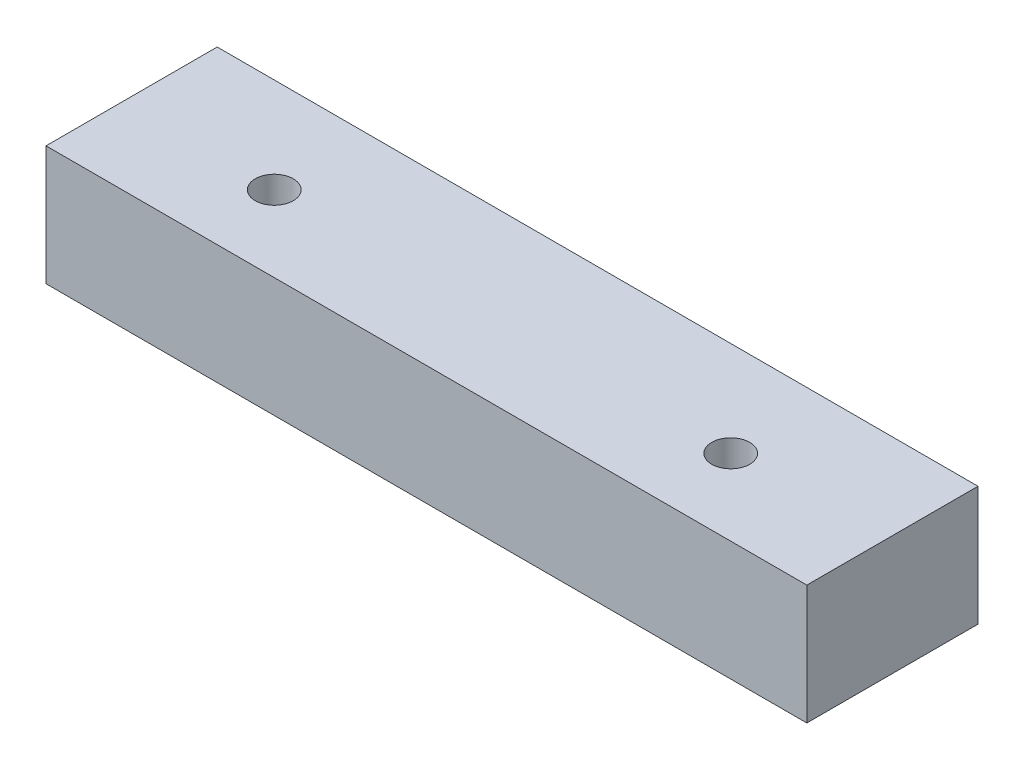
SolidWorks part; units mm, degrees
ref_plane "Front Plane" through (0, 0, 0) normal (0, 0, 1) x (1, 0, 0)
ref_plane "Top Plane" through (0, 0, 0) normal (0, 1, 0) x (1, 0, 0)
ref_plane "Right Plane" through (0, 0, 0) normal (1, 0, 0) x (0, 0, -1)
sketch "Sketch1" plane through (0, 0, 0) normal (0, 1, 0) x (1, 0, 0)
  line L0 (0, 0) -> (0, 9)
  line L1 (0, 9) -> (40, 9)
  line L2 (40, 9) -> (40, 0)
  line L3 (0, 0) -> (40, 0)
  dimension "D1" = 40
  dimension "D2" = 9
extrude "Boss-Extrude1" add sketch "Sketch1" along normal blind 6.28
sketch "Sketch2" plane through (0, 6.28, 0) normal (0, 1, 0) x (1, 0, 0)
  line L0 (0, 9) -> (8, 9)
  line L1 (40, 9) -> (0, 9) construction
  line L2 (8, 9) -> (8, 4)
  line L3 (8, 4) -> (32, 4)
  line L4 (0, 0) -> (0, 2.2) construction
  line L5 (0, 9) -> (0, 0) construction
  line L6 (0, 2.2) -> (19.4811, 2.2) construction
  line L7 (0, 2.2) -> (5, 2.2)
  line L8 (5, 2.2) -> (8, 2.2)
  line L9 (0, 0) -> (0, 0.75)
  line L10 (5, 2.2) -> (0, 0.75)
  line L11 (0, 0.75) -> (0, 2.2)
  line L12 (0, 0.75) -> (3, 0.75)
  line L13 (3, 0.75) -> (8, 2.2)
  line L14 (0, 0.75) -> (12.9505, 0.75) construction
  line L15 (16, 0.75) -> (13, 0.75)
  line L17 (8, 2.2) -> (11, 2.2)
  line L18 (8, 2.2) -> (13, 0.75)
  line L19 (11, 2.2) -> (16, 0.75)
  line L20 (24, 0.75) -> (27, 0.75)
  line L22 (40, 2.2) -> (35, 2.2)
  line L23 (40, 0) -> (40, 9) construction
  line L24 (35, 2.2) -> (32, 2.2)
  line L25 (32, 2.2) -> (29, 2.2)
  line L26 (24, 0.75) -> (29, 2.2)
  line L27 (27, 0.75) -> (32, 2.2)
  line L28 (40, 0.75) -> (37, 0.75)
  line L29 (32, 2.2) -> (37, 0.75)
  line L30 (35, 2.2) -> (40, 0.75)
  line L31 (3, 0.75) -> (13, 0.75)
  line L32 (11, 2.2) -> (16, 2.2)
  line L33 (16, 2.2) -> (16, 0)
  line L34 (0, 0) -> (40, 0) construction
  line L35 (24, 2.2) -> (29, 2.2)
  line L36 (27, 0.75) -> (37, 0.75)
  line L37 (40, 0.75) -> (40, 2.2)
  line L38 (16, 0) -> (24, 0)
  line L39 (24, 0) -> (24, 2.2)
  line L40 (16, 2.2) -> (24, 2.2)
  line L41 (16, 0.75) -> (24, 0.75)
  circle A0 centre (8, 4) radius 1
  circle A1 centre (32, 4) radius 1
  dimension "D2" = 2
  dimension "D4" = 2
  dimension "D1" = 8
  dimension "D3" = 24
  dimension "D5" = 5
  dimension "D6" = 2.2
  dimension "D7" = 0.75
  dimension "D8" = 5
  dimension "D9" = 3
  dimension "D10" = 3
  dimension "D11" = 3
  dimension "D12" = 3
  dimension "D13" = 3
  dimension "D14" = 5
  dimension "D15" = 3
  dimension "D16" = 3
  dimension "D17" = 3
  dimension "D18" = 5
  dimension "D19" = 5
extrude "Cut-Extrude1" cut sketch "Sketch2" along normal blind 5 and the other way blind 10 contours A1 | L2 A0 L3 | L3 A0 L2 region at (8.4244, 6.28, -4.4244) region at (32, 6.28, -4.9717) region at (7.8585, 6.28, -3.8585)
sketch "Sketch3" plane through (0, 0, -9) normal (0, 0, -1) x (-1, 0, 0)
  line L0 (-40, 6.28) -> (-32, 6.28) construction
  line L1 (-40, 6.28) -> (0, 6.28) construction
  line L2 (-32, 6.28) -> (-32, 4.28) construction
  line L3 (-32, 4.28) -> (-8, 4.28) construction
  line L4 (-8, 4.28) -> (-8, 6.28) construction
  line L5 (-8, 6.28) -> (0, 6.28) construction
  line L6 (-40, 6.28) -> (0, 6.28) construction
  circle A0 centre (-32, 4.28) radius 1.5
  circle A1 centre (-8, 4.28) radius 1.5
  point P12 (0, 5)
  point P15 (-40, 5)
  point P17 (0, 5)
  point P19 (-8, 5)
  dimension "D4" = 3
  dimension "D5" = 3
  dimension "D1" = 8
  dimension "D2" = 8
  dimension "D3" = 2
extrude "Cut-Extrude6" cut sketch "Sketch3" against normal blind 3.8
sketch "Sketch4" plane through (0, 0, -5.2) normal (0, 0, -1) x (-1, 0, 0)
  line L0 (-32, 4.28) -> (-33.5, 4.28) construction
  line L2 (-32, 4.28) -> (-30.5, 4.28) construction
  line L4 (-30.5, 4.53) -> (-33.5, 4.53)
  line L6 (-33.5, 4.03) -> (-30.5, 4.03)
  line L7 (-30.5, 4.03) -> (-30.5, 4.53)
  line L8 (-33.5, 4.03) -> (-33.5, 4.53)
  line L9 (-9.5, 4.28) -> (-6.5, 4.28) construction
  line L10 (-6.5, 4.03) -> (-6.5, 4.53)
  line L11 (-9.5, 4.03) -> (-9.5, 4.53)
  line L12 (-9.5, 4.53) -> (-6.5, 4.53)
  line L13 (-6.5, 4.03) -> (-9.5, 4.03)
  circle A0 centre (-32, 4.28) radius 1.5 construction
  circle A1 centre (-32, 4.28) radius 1.5 construction
  circle A2 centre (-8, 4.28) radius 1.5 construction
  circle A3 centre (-8, 4.28) radius 1.5 construction
  point P14 (-30.5, 4.28)
  point P15 (-33.5, 4.28)
  point P20 (-8, 4.28)
  point P22 (-6.5, 4.28)
  point P26 (-9.5, 4.28)
  dimension "D1" = 0.5
  dimension "D2" = 0.5
  dimension "D3" = 3
  dimension "D4" = 0.5
extrude "Cut-Extrude7" cut sketch "Sketch4" against normal blind 2.5
